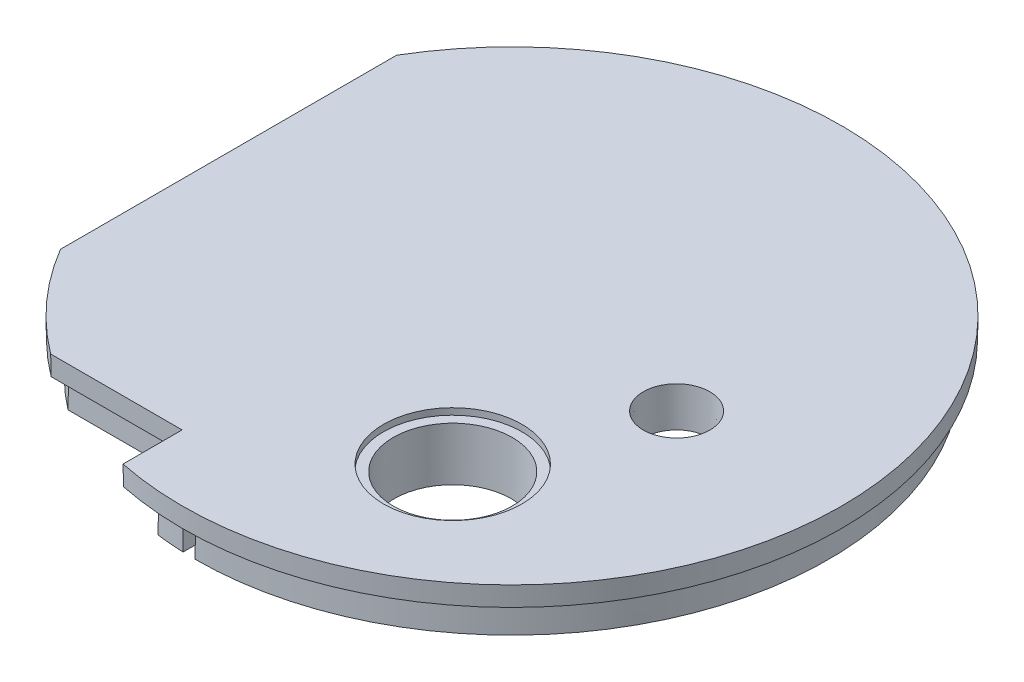
SolidWorks part; units mm, degrees
ref_plane "Front Plane" through (0, 0, 0) normal (0, 0, 1) x (1, 0, 0)
ref_plane "Top Plane" through (0, 0, 0) normal (0, 1, 0) x (1, 0, 0)
ref_plane "Right Plane" through (0, 0, 0) normal (1, 0, 0) x (0, 0, -1)
sketch "Sketch1" plane through (0, 0, 0) normal (0, 1, 0) x (1, 0, 0)
  line L0 (-43, 25.5147) -> (-43, -25.5147)
  line L1 (-30, -40) -> (-10, -40)
  line L2 (-10, -40) -> (-10, -48.9898)
  arc A0 (-43, -25.5147) -> (-30, -40) centre (0, 0) ccw
  arc A1 (-10, -48.9898) -> (-43, 25.5147) centre (0, 0) ccw
  dimension "D1" = 100
  dimension "D2" = 43
  dimension "D3" = 40
  dimension "D4" = 10
extrude "Boss-Extrude1" add sketch "Sketch1" along normal blind 3 draft 1 draft outward yes
sketch "Sketch2" plane through (0, 0, 0) normal (0, -1, 0) x (1, 0, 0)
  line L0 (-40.9781, 24.9959) -> (-40.9781, -24.9959)
  line L1 (-38.9781, 24.4276) -> (-38.9781, -24.4276)
  line L2 (-29.3258, 38) -> (-8, 38)
  line L4 (-28.6356, 36) -> (-8, 36)
  line L7 (-30, 40) -> (-10, 40) construction
  line L8 (-6, 45.607) -> (-6, 47.6235)
  line L10 (-8, -45.299) -> (-8, -47.3286)
  line L11 (-8, 38) -> (-8, 36)
  line L12 (-6, -45.607) -> (-6, -47.6235)
  line L13 (-2, 45.9565) -> (-2, 47.9583)
  line L14 (0, 46) -> (0, 48)
  line L15 (0, -46) -> (0, -48)
  line L16 (-2, -45.9565) -> (-2, -47.9583)
  arc A0 (-40.9781, -24.9959) -> (-8, -47.3286) centre (0, 0) ccw
  arc A1 (-38.9781, -24.4276) -> (-8, -45.299) centre (0, 0) ccw
  arc A2 (-29.3258, 38) -> (-40.9781, 24.9959) centre (0, 0) ccw
  arc A3 (-28.6356, 36) -> (-38.9781, 24.4276) centre (0, 0) ccw
  arc A4 (-2, 45.9565) -> (-6, 45.607) centre (0, 0) ccw
  arc A5 (-2, 47.9583) -> (-6, 47.6235) centre (0, 0) ccw
  arc A7 (-6, -45.607) -> (-2, -45.9565) centre (0, 0) ccw
  arc A8 (-6, -47.6235) -> (-2, -47.9583) centre (0, 0) ccw
  arc A9 (0, -48) -> (0, 48) centre (0, 0) ccw
  arc A10 (0, -46) -> (0, 46) centre (0, 0) ccw
  dimension "D1" = 96
  dimension "D2" = 92
  dimension "D3" = 2
  dimension "D4" = 2
  dimension "D7" = 2
extrude "Boss-Extrude2" add sketch "Sketch2" along normal blind 5 draft 1 draft outward yes
sketch "Sketch3" plane through (0, 0, 0) normal (0, -1, 0) x (1, 0, 0)
  line L0 (0, 0) -> (0, 55.6034) construction
  line L1 (0, 0) -> (17.6812, 0) construction
  circle A0 centre (25, 0) radius 5
  circle A1 centre (15, 24) radius 9
  dimension "D2" = 10
  dimension "D5" = 18
  dimension "D1" = 25
  dimension "D3" = 15
  dimension "D4" = 24
extrude "Cut-Extrude1" cut sketch "Sketch3" against normal blind 3 draft 1 draft outward yes
sketch "Sketch4" plane through (0, 0, 0) normal (0, -1, 0) x (1, 0, 0)
  circle A0 centre (25, 0) radius 8
  circle A1 centre (25, 0) radius 9
  circle A2 centre (25, 0) radius 5
  circle A3 centre (25, 0) radius 6
  dimension "D1" = 16
  dimension "D2" = 18
  dimension "D3" = 10
  dimension "D4" = 12
extrude "Boss-Extrude3" add sketch "Sketch4" along normal blind 3 draft 1 contours A0 | A1 draft outward yes
extrude "Boss-Extrude4" add sketch "Sketch4<3>" along normal blind 3 draft 1 contours A2 | A3 draft outward yes
sketch "Sketch4<3>" plane through (0, 0, 0) normal (0, -1, 0) x (1, 0, 0) same geometry as "Sketch4"
sketch "Sketch6" plane through (0, 0, 0) normal (0, -1, 0) x (1, 0, 0)
  circle A0 centre (15, 24) radius 9
  circle A1 centre (15, 24) radius 10.5
  dimension "D1" = 21
extrude "Boss-Extrude5" add sketch "Sketch6" along normal blind 6 draft 1 draft outward yes
sketch "Sketch7" plane through (0, 3, 0) normal (0, 1, 0) x (1, 0, 0)
  circle A0 centre (15, -24) radius 10.5
  circle A1 centre (15, -24) radius 9
  dimension "D1" = 21
  dimension "D2" = 18
extrude "Cut-Extrude2" cut sketch "Sketch7" against normal blind 1 draft 1 draft outward yes
